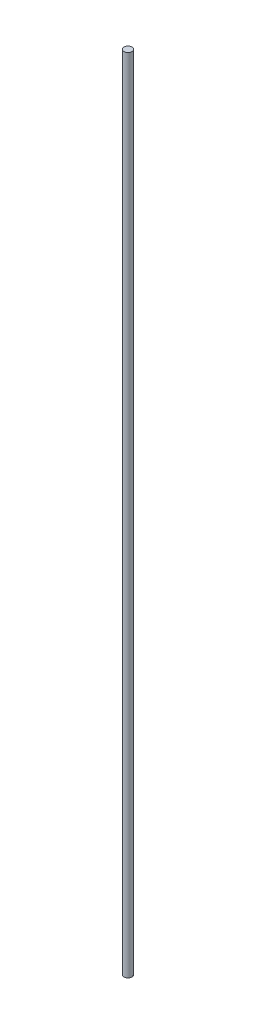
SolidWorks part; units mm, degrees
material "AISI 1020"
ref_plane "Front Plane" through (0, 0, 0) normal (0, 0, 1) x (1, 0, 0)
ref_plane "Top Plane" through (0, 0, 0) normal (0, 1, 0) x (1, 0, 0)
ref_plane "Right Plane" through (0, 0, 0) normal (1, 0, 0) x (0, 0, -1)
sketch "Sketch1" plane through (0, 0, 0) normal (0, 1, 0) x (1, 0, 0)
  circle A0 centre (0, 0) radius 4
  dimension "D1" = 8
extrude "Boss-Extrude1" add sketch "Sketch1" along normal blind 400 and the other way blind 400
cosmetic thread "Cosmetic Thread1"
